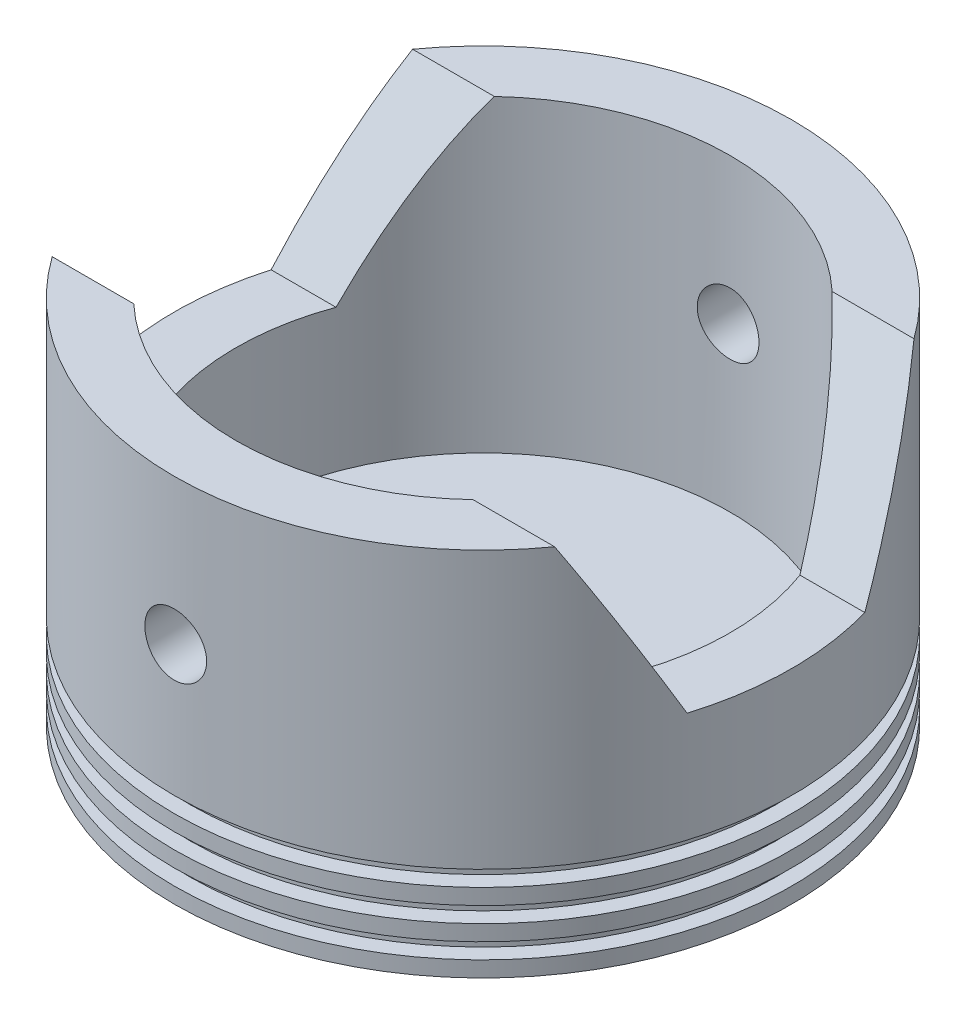
SolidWorks part; units mm, degrees
ref_plane "Front Plane" through (0, 0, 0) normal (0, 0, 1) x (1, 0, 0)
ref_plane "Top Plane" through (0, 0, 0) normal (0, 1, 0) x (1, 0, 0)
ref_plane "Right Plane" through (0, 0, 0) normal (1, 0, 0) x (0, 0, -1)
ref_axis "X Axis" through (-91.3614, 0, 0) along (1, 0, 0)
ref_axis "Z Axis" through (0, 0, 55) along (0, 0, -1)
ref_axis "Y Axis" through (0, 67.9804, 0) along (0, -1, 0)
sketch "Sketch1" plane through (0, 0, 0) normal (0, 1, 0) x (1, 0, 0)
  circle A0 centre (0, 0) radius 25
  dimension "D1" = 50
extrude "Boss-Extrude1" add sketch "Sketch1" along normal blind 30
sketch "Sketch2" plane through (0, 0, 0) normal (0, 0, 1) x (1, 0, 0)
  line L0 (0, 0) -> (0, 30) construction
  line L1 (25, 30) -> (-25, 30) construction
  line L2 (25, 0) -> (25, 30) construction
  line L3 (25, 2.54) -> (23.73, 2.54)
  line L4 (25, 2.54) -> (25, 1.27)
  line L5 (25, 1.27) -> (23.73, 1.27)
  line L6 (23.73, 2.54) -> (23.73, 1.27)
  line L7 (-25, 0) -> (25, 0) construction
  line L8 (25, 5.08) -> (23.73, 5.08)
  line L9 (25, 5.08) -> (25, 3.81)
  line L10 (25, 3.81) -> (23.73, 3.81)
  line L11 (23.73, 5.08) -> (23.73, 3.81)
  line L12 (25, 7.62) -> (23.73, 7.62)
  line L13 (25, 7.62) -> (25, 6.35)
  line L14 (25, 6.35) -> (23.73, 6.35)
  line L15 (23.73, 7.62) -> (23.73, 6.35)
  line L16 (25, 30) -> (-25, 30) construction
  dimension "D1" = 1.27
  dimension "D2" = 1.27
  dimension "D3" = 1.27
  dimension "D4" = 1.27
  dimension "D5" = 1.27
revolve "Cut-Revolve1" cut sketch "Sketch2" angle 360 about L0
ref_plane "Plane1" through (0, 15, 0) normal (0, 1, 0) x (1, 0, 0)
sketch "Sketch10" plane through (0, 30, 0) normal (0, 1, 0) x (1, 0, 0)
  circle A0 centre (0, 0) radius 20
  dimension "D1" = 40
extrude "Cut-Extrude1" cut sketch "Sketch10" against normal blind 25
sketch "Sketch11" plane through (0, 0, 0) normal (1, 0, 0) x (0, 0, -1)
  line L0 (0, 0) -> (0, 33.0471) construction
  line L1 (0, 16.5235) -> (6.8789, 16.5235)
  line L2 (6.8789, 16.5235) -> (14.5941, 30)
  line L3 (0, 16.5235) -> (-7.3645, 16.5235)
  line L4 (-7.3645, 16.5235) -> (-14.5402, 30)
  line L5 (-14.5402, 30) -> (14.5941, 30)
  dimension "D1" = 7.3645
extrude "Cut-Extrude2" cut sketch "Sketch11" against normal through all both and the other way through all
sketch "Sketch12" plane through (0, 0, 0) normal (0, 0, 1) x (1, 0, 0)
  circle A0 centre (0, 18.2102) radius 2.5
  dimension "D1" = 5
extrude "Cut-Extrude3" cut sketch "Sketch12" against normal through all both and the other way through all
